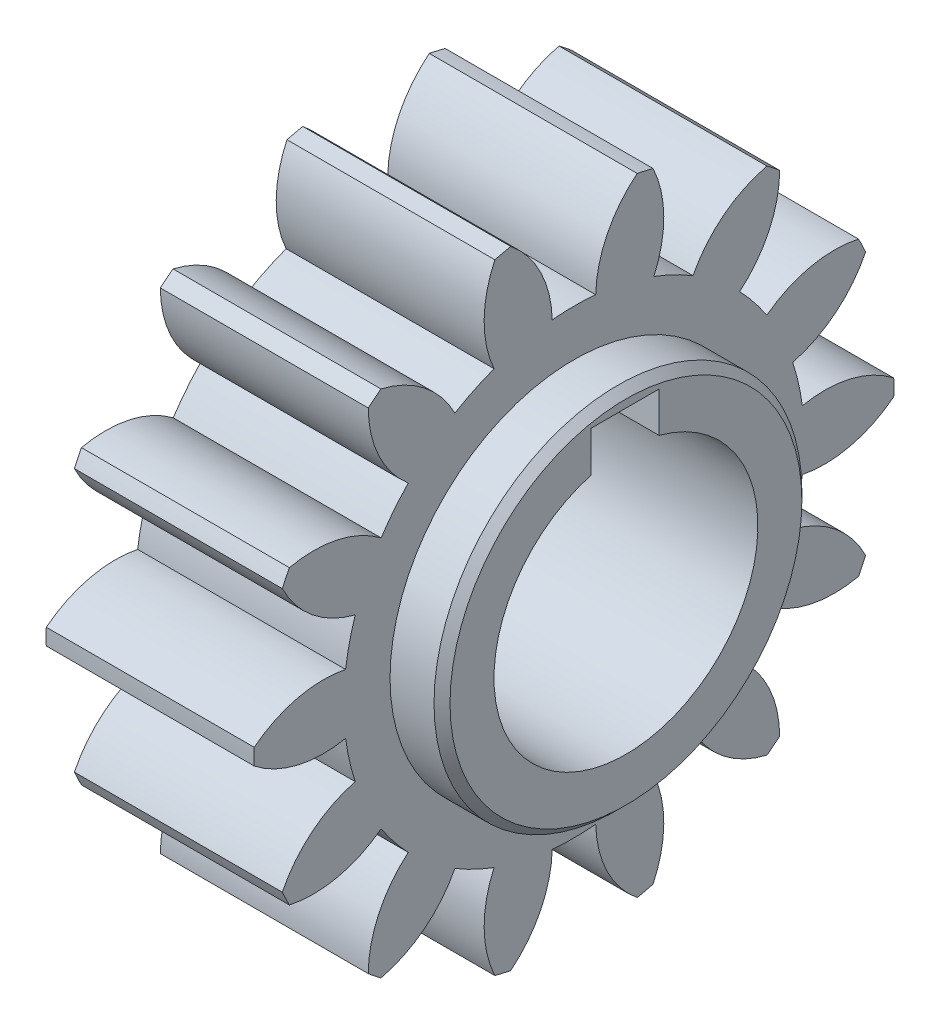
SolidWorks part; units mm, degrees
ref_plane "Plane1" through (0, 0, 0) normal (0, 0, 1) x (1, 0, 0)
ref_plane "Plane2" through (0, 0, 0) normal (0, 1, 0) x (1, 0, 0)
ref_plane "Plane3" through (0, 0, 0) normal (1, 0, 0) x (0, 0, -1)
sketch "HoldingSke" plane through (0, 0, 0) normal (0, 1, 0) x (1, 0, 0)
  line L0 (0, 0) -> (492.9102, -122.8963)
  line L1 (-15, 0) -> (100, 0) construction
  line L2 (0, 0) -> (-2.1039, 2.3779)
  line L3 (0, 0) -> (-11.863, 4.5341)
  line L4 (0, 0) -> (8.3795, 2.0892)
  line L5 (0, 0) -> (-47.5972, -17.7524)
  line L6 (0, 0) -> (-5.4745, -3.6936)
  line L7 (-2.1039, 2.3779) -> (8.8308, 51.9871)
  line L8 (-76.2, 54.61) -> (-67.9958, 54.61)
  line L9 (-71.009, 38.7566) -> (-53.1078, 45.2721)
  line L10 (-76.2, 71.12) -> (104.1128, 71.12)
  line L11 (0, 0) -> (-6.604, 0)
  line L12 (-76.2, 101.6) -> (-76.1492, 101.6)
  line L13 (24.9733, 27.94) -> (52.9518, 28.4284)
  line L14 (24.9733, 27.94) -> (25.0241, 27.9398)
  line L15 (24.9733, 27.94) -> (100.4021, 29.52)
  circle A0 centre (0, 0) radius 3.9688
  circle A1 centre (0, 0) radius 7.3152
  circle A2 centre (0, 0) radius 38.1
  circle A3 centre (0, 0) radius 3.9688
  dimension "Num_teeth" = 14
  dimension "H" = 19.05
  dimension "Pitch_radius" = 180.3128
  dimension "Width" = 6.604
  dimension "Thickness" = 6.604
sketch "BasProSke" plane through (0, 0, 0) normal (0, 1, 0) x (1, 0, 0)
  line L0 (-10, 0) -> (60, 0) construction
  line L1 (0, 0) -> (0, 10.16)
  line L2 (0, 0) -> (6.604, 0)
  line L3 (6.604, 0) -> (6.604, 10.16)
  line L4 (6.604, 10.16) -> (0, 10.16)
  dimension "Thickness" = 6.604
  dimension "Diameter" = 20.32
revolve "Base-Revolve" add sketch "BasProSke" angle 360 about L0
sketch "TooCutSke" plane through (0, 0, 0) normal (1, 0, 0) x (0, 0, -1)
  line L1 (0, 0) -> (0, 107) construction
  line L2 (0, 0) -> (-1.0842, 8.8236) construction
  line L3 (0, 0) -> (-3.9358, 17.2439) construction
  line L4 (-1.0842, 8.8236) -> (-1.9679, 8.6219) construction
  arc A0 (0.6903, 7.2826) -> (-0.6903, 7.2826) centre (0, 0) ccw
  arc A1 (2.0345, 9.9801) -> (-2.0345, 9.9801) centre (0, 0) ccw
  circle A2 centre (0, 0) radius 8.89 construction
  circle A3 centre (0, 0) radius 8.3539 construction
  arc A4 (-0.6903, 7.2826) -> (-2.0345, 9.9801) centre (-4.2452, 7.1948) ccw
  arc A5 (2.0345, 9.9801) -> (0.6903, 7.2826) centre (4.2452, 7.1948) ccw
extrude "ToothCut" cut sketch "TooCutSke" along normal through all
fillet "Breaks" [suppressed] radius 0.0254 tangent propagation no
fillet "RootFillets" [suppressed] radius 0.3048
pattern_circular "TeethCuts" count 14 every 25.714 about axis through (-10, 0, 0) along (1, 0, 0) of "ToothCut", "RootFillets", "Breaks"
sketch "HubNeaOneSke" plane through (0, 0, 0) normal (-1, 0, 0) x (0, 0, 1)
  circle A0 centre (0, 0) radius 7.3152
  dimension "Diameter" = 14.6304
extrude "HubNearOne" [suppressed] add sketch "HubNeaOneSke" along normal blind 44.1961
sketch "HubNeaBotSke" plane through (0, 0, 0) normal (-1, 0, 0) x (0, 0, 1)
  circle A0 centre (0, 0) radius 7.3152
  dimension "Diameter" = 14.6304
extrude "HubNearBoth" [suppressed] add sketch "HubNeaBotSke" along normal blind 22.098
ref_plane "FarPln" through (6.604, 0, 0) normal (1, 0, 0) x (0, 0, -1)
sketch "HubFarSke" plane through (6.604, 0, 0) normal (1, 0, 0) x (0, 0, -1)
  circle A0 centre (0, 0) radius 7.3152
  dimension "Diameter" = 14.6304
extrude "HubFar" [suppressed] add sketch "HubFarSke" along normal blind 22.098
sketch "BorSke" plane through (0, 0, 0) normal (1, 0, 0) x (0, 0, -1)
  circle A0 centre (0, 0) radius 4.191
  dimension "Diameter" = 8.382
extrude "Bore" cut sketch "BorSke" along normal mid plane 101.6001
sketch "KeySke" plane through (0, 0, 0) normal (1, 0, 0) x (0, 0, -1)
  line L0 (-0.127, 0) -> (-0.127, 4.2355)
  line L1 (-0.127, 4.2355) -> (0.127, 4.2355)
  line L2 (0.127, 4.2355) -> (0.127, 0)
  line L3 (0, 0) -> (0, 34) construction
  line L4 (-0.127, 0) -> (0.127, 0)
  dimension "Width" = 0.254
extrude "Keyway" [suppressed] cut sketch "KeySke" along normal mid plane 101.6001
pattern_circular "Keyway2" [suppressed] count 2 every 90 about axis through (-10, 0, 0) along (1, 0, 0) reverse direction yes
sketch "Sketch1" plane through (6.604, 0, 0) normal (1, 0, 0) x (0, 0, -1)
  circle A0 centre (0, 0) radius 4.191
  circle A1 centre (0, 0) radius 5.842
  dimension "D1" = 11.684
  dimension "D2" = 8.382
extrude "Boss-Extrude1" add sketch "Sketch1" along normal blind 1.651
sketch "Sketch2" plane through (0, 0, 0) normal (-1, 0, 0) x (0, 0, 1)
  line L0 (-1.0531, 0) -> (1.1059, 0)
  line L1 (1.1059, 0) -> (1.1059, 5.334)
  line L2 (1.1059, 5.334) -> (-1.0531, 5.334)
  line L3 (-1.0531, 5.334) -> (-1.0531, 0)
  dimension "D1" = 2.159
  dimension "D2" = 5.334
extrude "Cut-Extrude1" cut sketch "Sketch2" against normal through all
chamfer "Chamfer1" distance 0.254 angle 45 1 edges at (8.255, 0, -5.842)
equation "' \"Pitch@HoldingSke\" = 4"
equation "' \"Num_teeth@HoldingSke\" = 12"
equation "' \"Ap@HoldingSke\" =  20"
equation "' \"Ap@HoldingSke\" = 20"
equation "' \"Width@HoldingSke\" = 0.5"
equation "' \"Hub_dia@HoldingSke\"= 1"
equation "' \"Hub_dia@HoldingSke\" = 1"
equation "' \"Overall_len@HoldingSke\" = 1.0"
equation "' \"Bore@HoldingSke\" = 0.75"
equation "' \"T_dim@HoldingSke\" = 0.85"
equation "' \"Width@KeySke\" = 0.25"
equation "' \"Show_teeth@HoldingSke\" = 13"
equation "' \"Backlash@HoldingSke\" = 0.009"
equation "' \"Addendum_fac@HoldingSke\" = 1.0"
equation "' \"Dedendum_fac@HoldingSke\" = 1.25"
equation "' \"Dedendum_add@HoldingSke\" = 0.00005"
equation "' \"Clearance_fac@HoldingSke\" = 0.25"
equation "' \"Pitch@HoldingSke\" = 0.5"
equation "' \"Num_teeth@HoldingSke\" = 23"
equation "' \"Show_teeth@HoldingSke\" = 23"
equation "' \"Backlash@HoldingSke\" = 0.0375"
equation "\"Overcut_dia@TooCutSke\" = (\"Num_teeth@HoldingSke\" + 2 * \"Addendum_fac@HoldingSke\") / \"Pitch@HoldingSke\" + 0.002"
equation "\"Pitch_dia@TooCutSke\" = \"Num_teeth@HoldingSke\" / \"Pitch@HoldingSke\""
equation "\"Base_dia@TooCutSke\" = \"Num_teeth@HoldingSke\" / \"Pitch@HoldingSke\" * cos((\"Ap@HoldingSke\"  * 3.14159265 / 180))"
equation "\"Root_dia@TooCutSke\" = (\"Num_teeth@HoldingSke\" + 2) / \"Pitch@HoldingSke\" - 2 * (\"Addendum_fac@HoldingSke\" + \"Dedendum_fac@HoldingSke\") / \"Pitch@HoldingSke\" - \"Dedendum_add@HoldingSke\" * 2"
equation "\"Half_ang@TooCutSke\" = 180 / \"Num_teeth@HoldingSke\""
equation "\"Half_CT@TooCutSke\" = \"Num_teeth@HoldingSke\" / \"Pitch@HoldingSke\" * sin((3.14159265 / 2 / \"Num_teeth@HoldingSke\")) / 2 - 7 * \"Backlash@HoldingSke\" / 4"
equation "\"Flank_rad@TooCutSke\" = \"Num_teeth@HoldingSke\" / \"Pitch@HoldingSke\" / 5"
equation "\"Radius@RootFillets\" = \"Clearance_fac@HoldingSke\" / \"Pitch@HoldingSke\" + \"Dedendum_add@HoldingSke\""
equation "\"Break_rad@Breaks\" = 0.02 / \"Pitch@HoldingSke\""
equation "\"Thickness@HoldingSke\" = \"Width@HoldingSke\""
equation "\"OAL@HoldingSke\" = \"Thickness@HoldingSke\""
equation "\"MHD@HoldingSke\" = (\"Num_teeth@HoldingSke\" + 2) / \"Pitch@HoldingSke\" - 2 * (\"Addendum_fac@HoldingSke\" + \"Dedendum_fac@HoldingSke\")  / \"Pitch@HoldingSke\" - \"Dedendum_add@HoldingSke\" * 2"
equation "\"MBD@HoldingSke\" = (\"Num_teeth@HoldingSke\" + 2) / \"Pitch@HoldingSke\" - 2 * (\"Addendum_fac@HoldingSke\" + \"Dedendum_fac@HoldingSke\")  / \"Pitch@HoldingSke\" - \"Dedendum_add@HoldingSke\" * 2 - 0.002"
equation "\"MHD@HoldingSke\" = ((sgn( \"MHD@HoldingSke\" - \"Hub_dia@HoldingSke\" )-1)*( \"MHD@HoldingSke\" - \"Hub_dia@HoldingSke\" ))/-2+ \"Hub_dia@HoldingSke\""
equation "\"MBD@HoldingSke\" = ((sgn( \"MBD@HoldingSke\" - \"Bore@HoldingSke\" )-1)*( \"MBD@HoldingSke\" - \"Bore@HoldingSke\" ))/-2+ \"Bore@HoldingSke\""
equation "\"OAL@HoldingSke\" = ((sgn( \"OAL@HoldingSke\" - \"Overall_len@HoldingSke\" )+1)*( \"OAL@HoldingSke\" - \"Overall_len@HoldingSke\" ))/2 + \"Overall_len@HoldingSke\" + 0.000002"
equation "\"Num_teeth@TeethCuts\" = int( \"Show_teeth@HoldingSke\" ) + 1"
equation "\"Num_teeth@TeethCuts\" = ((sgn( \"Num_teeth@TeethCuts\" - \"Num_teeth@HoldingSke\" )-1)*( \"Num_teeth@TeethCuts\" - \"Num_teeth@HoldingSke\" ))/-2+ \"Num_teeth@HoldingSke\""
equation "\"Num_teeth@TeethCuts\" = ((sgn( \"Num_teeth@TeethCuts\" - 2.0)+1)*( \"Num_teeth@TeethCuts\" - 2.0))/2 +2.0"
equation "\"Angle@TeethCuts\" = 360.0 / \"Num_teeth@HoldingSke\""
equation "\"Diameter@BasProSke\" = (\"Num_teeth@HoldingSke\" + 2 * \"Addendum_fac@HoldingSke\") / \"Pitch@HoldingSke\""
equation "\"Thickness@BasProSke\"  = \"Thickness@HoldingSke\""
equation "' \"Fillet_rad@BasProSke\" =  \"Thickness@HoldingSke\" * 0.05"
equation "' \"Fillet_rad@BasProSke\" = \"Thickness@HoldingSke\" * 0.05"
equation "\"MHD@HoldingSke\" = ((sgn( \"MHD@HoldingSke\" - \"Root_dia@TooCutSke\" )-1)*( \"MHD@HoldingSke\" - \"Root_dia@TooCutSke\" ))/-2+ \"Root_dia@TooCutSke\""
equation "\"Diameter@HubNeaOneSke\" = \"MHD@HoldingSke\""
equation "\"Length@HubNearOne\" = \"OAL@HoldingSke\" - \"Thickness@BasProSke\""
equation "\"Diameter@HubNeaBotSke\" = \"MHD@HoldingSke\""
equation "\"Length@HubNearBoth\" = ( \"OAL@HoldingSke\" - \"Thickness@BasProSke\" ) / 2.0"
equation "\"Thickness@FarPln\" = \"Thickness@BasProSke\""
equation "\"Diameter@HubFarSke\" = \"MHD@HoldingSke\""
equation "\"Length@HubFar\" = ( \"OAL@HoldingSke\" - \"Thickness@BasProSke\" ) / 2.0"
equation "\"D1@Bore\" = \"OAL@HoldingSke\" * 2.0"
equation "\"D1@Keyway\" = \"OAL@HoldingSke\" * 2.0"
equation "\"Offset@KeySke\" = \"T_dim@HoldingSke\" - \"MBD@HoldingSke\" / 2.0"
